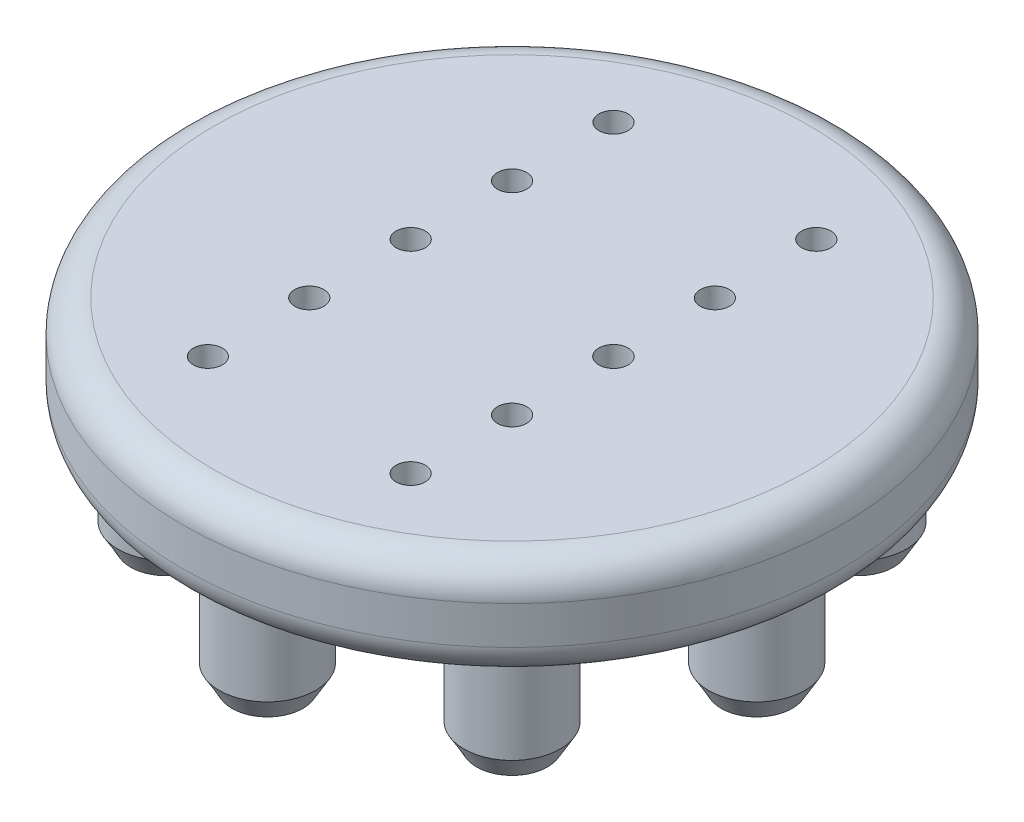
SolidWorks part; units mm, degrees
ref_plane "Front Plane" through (0, 0, 0) normal (0, 0, 1) x (1, 0, 0)
ref_plane "Top Plane" through (0, 0, 0) normal (0, 1, 0) x (1, 0, 0)
ref_plane "Right Plane" through (0, 0, 0) normal (1, 0, 0) x (0, 0, -1)
sketch "Sketch1" plane through (0, 0, 0) normal (0, 1, 0) x (1, 0, 0)
  circle A0 centre (0, 0) radius 26
  circle A1 centre (-13.6472, 13.6472) radius 3.8
  circle A2 centre (0, 19.3) radius 3.8
  circle A3 centre (13.6472, 13.6472) radius 3.8
  circle A4 centre (19.3, 0) radius 3.8
  circle A5 centre (13.6472, -13.6472) radius 3.8
  circle A6 centre (0, -19.3) radius 3.8
  circle A7 centre (-13.6472, -13.6472) radius 3.8
  circle A8 centre (-19.3, 0) radius 3.8
  circle A9 centre (0, 0) radius 6.25
  point P5 (0, 0)
  circle B0 centre (0, 19.3) radius 3.8
  circle B1 centre (13.6472, 13.6472) radius 3.8
  circle B2 centre (0, 0) radius 6.25
  circle B3 centre (-13.6472, 13.6472) radius 3.8
  circle B4 centre (-19.3, 0) radius 3.8
  circle B5 centre (-13.6472, -13.6472) radius 3.8
  circle B6 centre (0, -19.3) radius 3.8
  circle B7 centre (13.6472, -13.6472) radius 3.8
  circle B8 centre (19.3, 0) radius 3.8
sketch_block_instance "Block2-9"
sketch_block "Block2" parameters "D2"=3.9779, "D1"=8
extrude "Boss-Extrude1" add sketch "Sketch1" along normal blind 8 contours A0
sketch "Sketch2" plane through (0, 0, 0) normal (0, -1, 0) x (1, 0, 0)
  circle A1 centre (0, 0) radius 6.1
extrude "Cut-Extrude2" cut sketch "Sketch2" against normal blind 3
extrude "Boss-Extrude3" add sketch "Sketch1<11>" against normal blind 9 contours A1 | A2 | A3 | A4 | A5 | A6 | A7 | A8
sketch "Sketch1<11>" plane through (0, 0, 0) normal (0, 1, 0) x (1, 0, 0) same geometry as "Sketch1"
fillet "Fillet1" radius 2.5 2 edges at (0, 0, 26) (0, 8, 26)
sketch "Sketch3" plane through (0, 8, 0) normal (0, 1, 0) x (1, 0, 0)
  line L1 (-8, -16) -> (8, -16)
  line L2 (-8, -16) -> (-8, 16)
  line L3 (-8, 16) -> (8, 16)
  line L4 (8, -16) -> (8, 16)
  line L5 (-8, -16) -> (8, 16) construction
  line L6 (-8, 16) -> (8, -16) construction
  circle A0 centre (-8, 16) radius 1.15
  circle A1 centre (8, 16) radius 1.15
  circle A2 centre (-8, 8) radius 1.15
  circle A3 centre (8, 8) radius 1.15
  circle A4 centre (-8, -8) radius 1.15
  circle A5 centre (8, -8) radius 1.15
  circle A6 centre (-8, -16) radius 1.15
  circle A7 centre (8, -16) radius 1.15
  circle A8 centre (-8, 0) radius 1.15
  circle A9 centre (8, 0) radius 1.1602
  point P0 (0, 0)
  point P6 (-8, 8)
  point P7 (-8, 0)
  point P8 (8, 8)
  point P9 (8, 0)
  point P10 (8, -8)
  point P11 (-49.3985, 2.8418)
  point P12 (-8, -8)
  dimension "D1" = 16
  dimension "D2" = 32
extrude "Cut-Extrude3" cut sketch "Sketch3" against normal blind 6 contours A0 | A2 | A1 | A3 | A4 | A5 | A6 | A7 | A8 | A9
chamfer "Chamfer1" distance 1 angle 60 8 edges at (-13.6472, -9, -9.8472) (0, -9, -15.5) (13.6472, -9, -9.8472) (19.3, -9, 3.8) (13.6472, -9, 17.4472) (0, -9, 23.1) (-13.6472, -9, 17.4472) (-19.3, -9, 3.8) first distance on face at (-13.6472, -9, -9.8472) first distance on face at (0, -9, -15.5) first distance on face at (13.6472, -9, -9.8472) first distance on face at (19.3, -9, 3.8) first distance on face at (13.6472, -9, 17.4472) first distance on face at (0, -9, 23.1) first distance on face at (-13.6472, -9, 17.4472) first distance on face at (-19.3, -9, 3.8)
